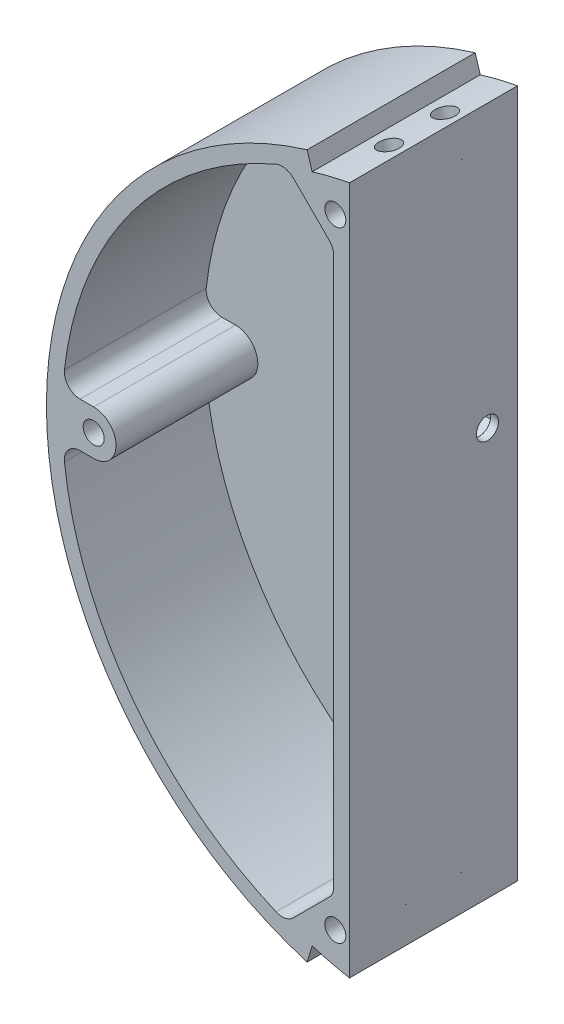
SolidWorks part; units mm, degrees
ref_plane "Front Plane" through (0, 0, 0) normal (0, 0, 1) x (1, 0, 0)
ref_plane "Top Plane" through (0, 0, 0) normal (0, 1, 0) x (1, 0, 0)
ref_plane "Right Plane" through (0, 0, 0) normal (1, 0, 0) x (0, 0, -1)
sketch "Sketch1" plane through (0, 0, 0) normal (0, 0, 1) x (1, 0, 0)
  line L0 (-12.3, -68.9109) -> (-12.3, 68.9109)
  line L1 (-15, 59) -> (-15, -59) construction
  line L5 (-61, 0) -> (0, 0) construction
  circle A2 centre (-15, 59) radius 1.25
  circle A4 centre (-61, 0) radius 1.25
  circle A5 centre (-15, -59) radius 1.25
  arc A6 (-12.3, 68.9109) -> (-12.3, -68.9109) centre (0, 0) ccw
  circle A7 centre (0, 0) radius 65.5 construction
  circle A8 centre (-15, 59) radius 3 construction
  circle A9 centre (-61, 0) radius 3 construction
  circle A10 centre (-15, -59) radius 3 construction
  point P6 (-15, 0)
  dimension "D2" = 2.5
  dimension "D6" = 118
  dimension "D7" = 131
  dimension "D8" = 2.5
  dimension "D4" = 70
  dimension "D3" = 2.5
  dimension "D10" = 6
  dimension "D1" = 12.3
  dimension "D5" = 15
  dimension "D9" = 61
extrude "Boss-Extrude2" add sketch "Sketch1" along normal blind 32
shell "Shell1" thickness 3 removed face at (-13.75, 59, 32)
sketch "Sketch10" plane through (0, 0, 3) normal (0, 0, 1) x (1, 0, 0)
  line L0 (-15.3, 53.2896) -> (-24.4068, 62.3964)
  line L1 (-15.3, -54.7606) -> (-15.3, 54.7606) construction
  line L2 (-15.3, -53.2896) -> (-24.4068, -62.3964)
  line L3 (-15.3, -54.7606) -> (-15.3, 54.7606) construction
  line L4 (-15.3, 65.2297) -> (-15.3, 60.2135)
  line L5 (-15.3, 57.7865) -> (-15.3, 53.2896)
  line L6 (-15.3, 63.2394) -> (-15.3, 65.2297) construction
  line L7 (-15.3, -65.2297) -> (-15.3, -60.2135)
  line L8 (-15.3, -57.7865) -> (-15.3, -53.2896)
  line L9 (-61, -4.25) -> (-63.588, -4.25)
  line L10 (-61, 4.25) -> (-63.588, 4.25)
  arc A0 (-24.4068, 62.3964) -> (-15.3, 65.2297) centre (0, 0) cw
  arc A1 (-63.588, -4.25) -> (-66.5687, -7.5898) centre (-63.588, -7.25) ccw
  arc A2 (-15.3, 65.2297) -> (-15.3, -65.2297) centre (0, 0) ccw construction
  arc A3 (-15.3, 65.2297) -> (-15.3, -65.2297) centre (0, 0) ccw construction
  arc A4 (-15.3, -54.7606) -> (-15.3, -63.2394) centre (-15, -59) ccw construction
  arc A5 (-15.3, 63.2394) -> (-15.3, 54.7606) centre (-15, 59) ccw construction
  arc A6 (-15.3, -65.2297) -> (-24.4068, -62.3964) centre (0, 0) cw
  circle A7 centre (-15, 59) radius 1.25 construction
  arc A8 (-15.3, 60.2135) -> (-15.3, 57.7865) centre (-15, 59) ccw
  circle A9 centre (-15, -59) radius 1.25 construction
  arc A10 (-15.3, -60.2135) -> (-15.2655, -57.7785) centre (-15, -59) cw
  arc A11 (-61, 4.25) -> (-61, -4.25) centre (-61, 0) cw
  circle A12 centre (-61, 0) radius 4.25 construction
  circle A13 centre (-61, 0) radius 4.25 construction
  arc A14 (-63.588, 4.25) -> (-66.5687, 7.5898) centre (-63.588, 7.25) cw
  arc A15 (-66.5687, 7.5898) -> (-66.5687, -7.5898) centre (0, 0) ccw
  circle A16 centre (-61, 0) radius 1.25
  point P57 (-66.8651, 4.25)
  line M8 (-15.3, 63.2394) -> (-15.3, 65.2297)
  arc M9 (-15.3, 65.2297) -> (-15.3, -65.2297) centre (0, 0) ccw
  line M10 (-15.3, -65.2297) -> (-15.3, -63.2394)
  arc M11 (-15.3, -63.2394) -> (-15.3, -54.7606) centre (-15, -59) cw
  line M12 (-15.3, -54.7606) -> (-15.3, 54.7606)
  arc M13 (-15.3, 54.7606) -> (-15.3, 63.2394) centre (-15, 59) cw
  circle M14 centre (-61, 0) radius 4.25
  dimension "D3" = 3
  dimension "D1" = 135
  dimension "D2" = 135
extrude "Boss-Extrude6" add sketch "Sketch10" along normal up to surface (29 mm away) contours L10 A14 A1 L9 M9 M14 | A16 M14 | L7 A10 L8 M11 | L2 M11 M9 M10 | L0 M13 M8 M9 | A8 L4 L5 M13 | L2 M12 M11 | L0 M12 M13 region at (-16.0191, 54.4613, 3) region at (-17.0571, 59, 3) region at (-19.7689, 61.9404, 3) region at (-16.0191, -54.4613, 3) region at (-19.7689, -61.9404, 3) region at (-17.0571, -59, 3) region at (-65.581, 0, 3) region at (-58.0798, 2.9202, 3) up to face at (-25.2333, 0, 32)
fillet "Fillet1" radius 3 4 edges at (-24.4068, -62.3964, 17.5) (-15.3, -53.2896, 17.5) (-15.3, 53.2896, 17.5) (-24.4068, 62.3964, 17.5)
sketch "Sketch11" plane through (-12.3, 0, 0) normal (1, 0, 0) x (0, 0, -1)
  line L2 (0, -68.9109) -> (0, 68.9109) construction
  circle A0 centre (-5.75, 12) radius 2.1
  circle A1 centre (-5.75, 12) radius 0.75 construction
  dimension "D1" = 4.2
  dimension "D3" = 1.5
  dimension "D4" = 5
  dimension "D2" = 12
extrude "Cut-Extrude4" cut sketch "Sketch11" against normal blind 5
sketch "Sketch12" plane through (0, 0, 32) normal (0, 0, 1) x (1, 0, 0)
  circle A0 centre (-15, -59) radius 2
  circle A1 centre (-61, 0) radius 2
  circle A2 centre (-15, 59) radius 2
  dimension "D1" = 4
extrude "Thread insert holes" cut sketch "Sketch12" against normal blind 4.78
sketch "Sketch13" plane through (0, 0, 0) normal (0, 0, -1) x (-1, 0, 0)
  circle A0 centre (15, 59) radius 2
  circle A1 centre (61, 0) radius 2
  circle A2 centre (15, -59) radius 2
  dimension "D1" = 4
extrude "Cut-Extrude6" cut sketch "Sketch13" against normal blind 4.78
sketch "Sketch14" plane through (0, 0, 0) normal (0, 0, 1) x (1, 0, 0)
  line L0 (-12.3, -68.9109) -> (-12.3, 68.9109) construction
  line L1 (-20.3654, -66.972) -> (0, 0) construction
  line L2 (0, 0) -> (-20.3654, 66.972) construction
  line L3 (-19.4053, -63.8148) -> (-20.3654, -66.972)
  line L4 (-19.4053, 63.8148) -> (-20.3654, 66.972)
  line L5 (-12.3, 65.5561) -> (-12.3, 68.9109)
  line L6 (-12.3, -65.5561) -> (-12.3, -68.9109)
  arc A0 (-12.3, 68.9109) -> (-20.3654, 66.972) centre (0, 0) ccw
  arc A1 (-12.3, -68.9109) -> (-20.3654, -66.972) centre (0, 0) cw
  arc A2 (-12.3, -65.5561) -> (-19.4053, -63.8148) centre (0, 0) cw
  arc A3 (-12.3, 65.5561) -> (-19.4053, 63.8148) centre (0, 0) ccw
  dimension "D3" = 3.3
  dimension "D4" = 3.3
  dimension "D1" = 8.3
  dimension "D2" = 8.3
extrude "Cut-Extrude7" cut sketch "Sketch14" along normal blind 32
sketch "Sketch15" plane through (0, 0, 0) normal (0, 0, 1) x (1, 0, 0)
  line L0 (-12.3, -65.5561) -> (-12.3, 65.5561) construction
  arc A0 (-12.3, -68.9109) -> (-20.0782, -67.0587) centre (0, 0) cw
  arc A1 (-12.3, 68.9109) -> (-20.0782, 67.0587) centre (0, 0) ccw
  circle A2 centre (0, 0) radius 70 construction
  point P11 (-16.2155, 68.0959)
  point P13 (-16.2155, -68.0959)
  dimension "D2" = 140
  dimension "D1" = 8
  dimension "D3" = 8
sketch3d "3DSketch1"
  line L0 (-16.2155, -68.0959, 0) -> (-16.2155, -68.0959, 32)
  line L2 (-16.2155, 68.0959, 0) -> (-16.2155, 68.0959, 32)
  arc A0 (-12.3, 68.9109, 0) -> (-20.0782, 67.0587, 0) centre (0, 0, 0) ccw construction
  point P9 (0, 0, 70)
ref_plane "Plane1" through (-16.2155, 68.0959, 0) normal (-0.2317, 0.9728, 0) x (0.9728, 0.2317, 0)
ref_plane "Plane2" through (-16.2155, -68.0959, 0) normal (-0.2317, -0.9728, 0) x (-0.9728, 0.2317, 0)
sketch "Sketch16" plane through (-16.2155, 68.0959, 0) normal (-0.2317, 0.9728, 0) x (0.9728, 0.2317, 0)
  line L0 (0, 0) -> (0, -32) construction
  circle A0 centre (0, -10.6667) radius 1.65
  circle A1 centre (0, -21.3333) radius 1.65
  dimension "D1" = 10.6667
  dimension "D3" = 3.3
  dimension "D2" = 21.3333
extrude "Cut-Extrude8" cut sketch "Sketch16" against normal blind 10
sketch "Sketch17" plane through (-16.2155, -68.0959, 0) normal (-0.2317, -0.9728, 0) x (-0.9728, 0.2317, 0)
  line L0 (0, 0) -> (0, -32) construction
  circle A0 centre (0, -10.6667) radius 1.65
  circle A1 centre (0, -21.3333) radius 1.65
  dimension "D1" = 10.6667
  dimension "D2" = 21.3333
  dimension "D3" = 3.3
extrude "Cut-Extrude9" cut sketch "Sketch17" against normal blind 10
sketch "Sketch18" plane through (-16.2155, 68.0959, 0) normal (-0.2317, 0.9728, 0) x (0.9728, 0.2317, 0)
  circle A0 centre (0, -10.6667) radius 2
  circle A1 centre (0, -21.3333) radius 2
  dimension "D1" = 4
  dimension "D2" = 4
extrude "Cut-Extrude10" cut sketch "Sketch18" against normal blind 8
sketch "Sketch19" plane through (-16.2155, -68.0959, 0) normal (-0.2317, -0.9728, 0) x (-0.9728, 0.2317, 0)
  circle A0 centre (0, -10.6667) radius 2
  circle A1 centre (0, -21.3333) radius 2
  dimension "D1" = 4
extrude "Cut-Extrude11" cut sketch "Sketch19" against normal blind 8
sketch "Sketch23" plane through (0, 0, 3) normal (0, 0, 1) x (1, 0, 0)
  line L0 (-15.3, -52.047) -> (-15.3, 52.047)
  line L1 (-16.1787, 54.1683) -> (-22.9967, 60.9863)
  line L2 (-22.9967, -60.9863) -> (-16.1787, -54.1683)
  line L3 (-63.588, -4.25) -> (-61, -4.25)
  line L4 (-61, 4.25) -> (-63.588, 4.25)
  arc A0 (-15.3, 52.047) -> (-16.1787, 54.1683) centre (-18.3, 52.047) ccw
  arc A1 (-22.9967, 60.9863) -> (-26.2954, 61.6243) centre (-25.118, 58.865) ccw
  arc A2 (-26.2954, 61.6243) -> (-66.5687, 7.5898) centre (0, 0) ccw
  arc A3 (-15.3, -52.047) -> (-16.1787, -54.1683) centre (-18.3, -52.047) cw
  arc A4 (-22.9967, -60.9863) -> (-26.2954, -61.6243) centre (-25.118, -58.865) cw
  arc A5 (-26.2954, -61.6243) -> (-66.5687, -7.5898) centre (0, 0) cw
  arc A6 (-66.5687, -7.5898) -> (-63.588, -4.25) centre (-63.588, -7.25) cw
  arc A7 (-66.5687, 7.5898) -> (-63.588, 4.25) centre (-63.588, 7.25) ccw
  arc A8 (-61, 4.25) -> (-61, -4.25) centre (-61, 0) cw
extrude "Boss-Extrude8" add sketch "Sketch23" along normal blind 2
sketch "Sketch20" plane through (-15.3, 0, 0) normal (-1, 0, 0) x (0, 0, 1)
  line L1 (5.75, 7.208) -> (9.9, 9.604)
  line L2 (9.9, 9.604) -> (9.9, 14.396)
  line L3 (9.9, 14.396) -> (5.75, 16.792)
  line L4 (5.75, 16.792) -> (1.6, 14.396)
  line L5 (1.6, 14.396) -> (1.6, 9.604)
  line L6 (1.6, 9.604) -> (5.75, 7.208)
  circle A1 centre (5.75, 12) radius 4.15 construction
  dimension "D1" = 8.3
extrude "Cut-Extrude12" cut sketch "Sketch20" against normal blind 1.5 and the other way blind 5
